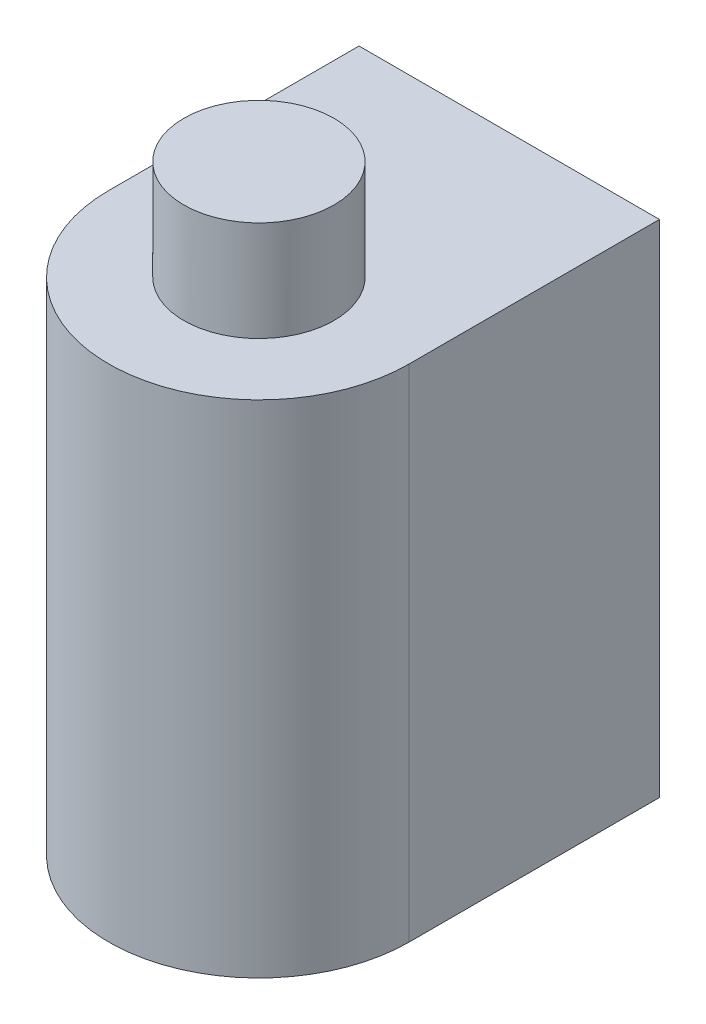
SolidWorks part; units mm, degrees
ref_plane "Ebene vorne" through (0, 0, 0) normal (0, 0, 1) x (1, 0, 0)
ref_plane "Ebene oben" through (0, 0, 0) normal (0, 1, 0) x (1, 0, 0)
ref_plane "Ebene rechts" through (0, 0, 0) normal (1, 0, 0) x (0, 0, -1)
sketch "Sketch1" plane through (0, 0, 0) normal (0, 0, 1) x (1, 0, 0)
  line L1 (-3, 5) -> (3, 5)
  line L2 (-3, 5) -> (-3, -5)
  line L3 (-3, -5) -> (3, -5)
  line L4 (3, 5) -> (3, -5)
  line L5 (-3, 5) -> (3, -5) construction
  line L6 (-3, -5) -> (3, 5) construction
  point P0 (0, 0)
  dimension "D1" = 6
  dimension "D2" = 10
extrude "Boss-Extrude1" add sketch "Sketch1" along normal blind 8
fillet "Fillet2" 2 edges at (3, 0, 8) (-3, 0, 8) type full round first side face at (3, 0, 4) second side face at (-3, 0, 4) middle face at (0, 0, 8)
sketch "Sketch2" plane through (0, 5, 0) normal (0, 1, 0) x (1, 0, 0)
  circle A0 centre (0, -5) radius 1.5
  dimension "D1" = 3
extrude "Boss-Extrude2" add sketch "Sketch2" along normal blind 2
